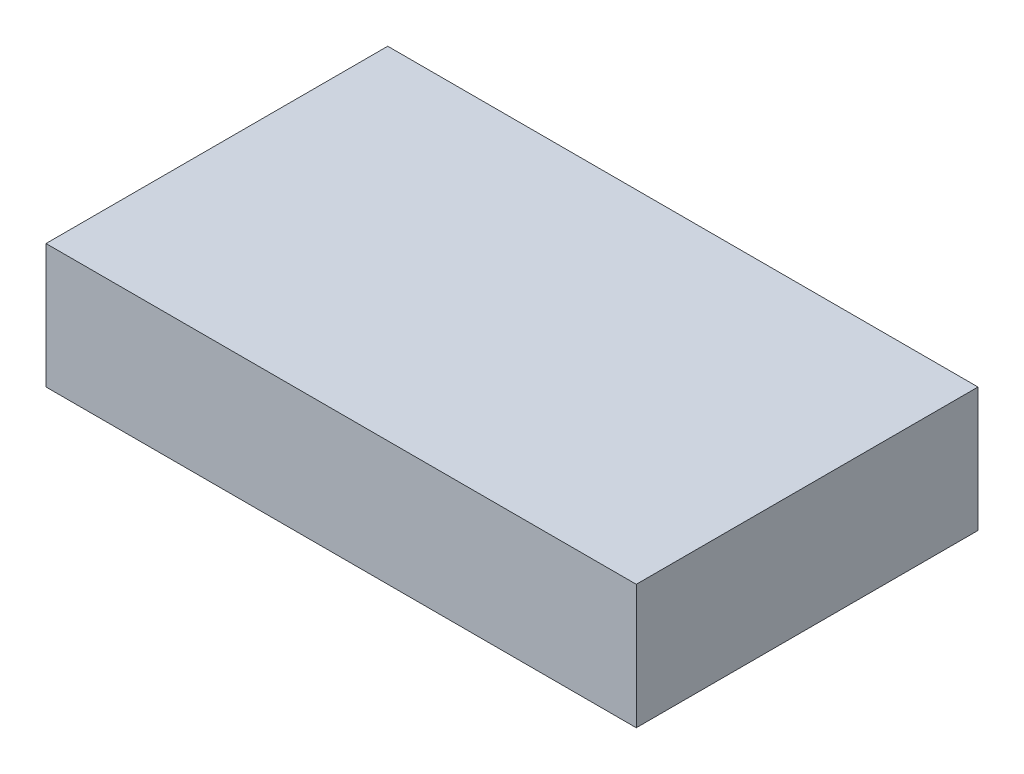
SolidWorks part; units mm, degrees
ref_plane "Front Plane" through (0, 0, 0) normal (0, 0, 1) x (1, 0, 0)
ref_plane "Top Plane" through (0, 0, 0) normal (0, 1, 0) x (1, 0, 0)
ref_plane "Right Plane" through (0, 0, 0) normal (1, 0, 0) x (0, 0, -1)
sketch "Sketch1" plane through (0, 0, 0) normal (0, 1, 0) x (1, 0, 0)
  line L1 (-47.4625, 32.2918) -> (73.1875, 32.2918)
  line L2 (-47.4625, 32.2918) -> (-47.4625, -37.5582)
  line L3 (-47.4625, -37.5582) -> (73.1875, -37.5582)
  line L4 (73.1875, 32.2918) -> (73.1875, -37.5582)
  dimension "D1" = 69.85
  dimension "D2" = 120.65
extrude "Boss-Extrude1" add sketch "Sketch1" along normal blind 25.4
